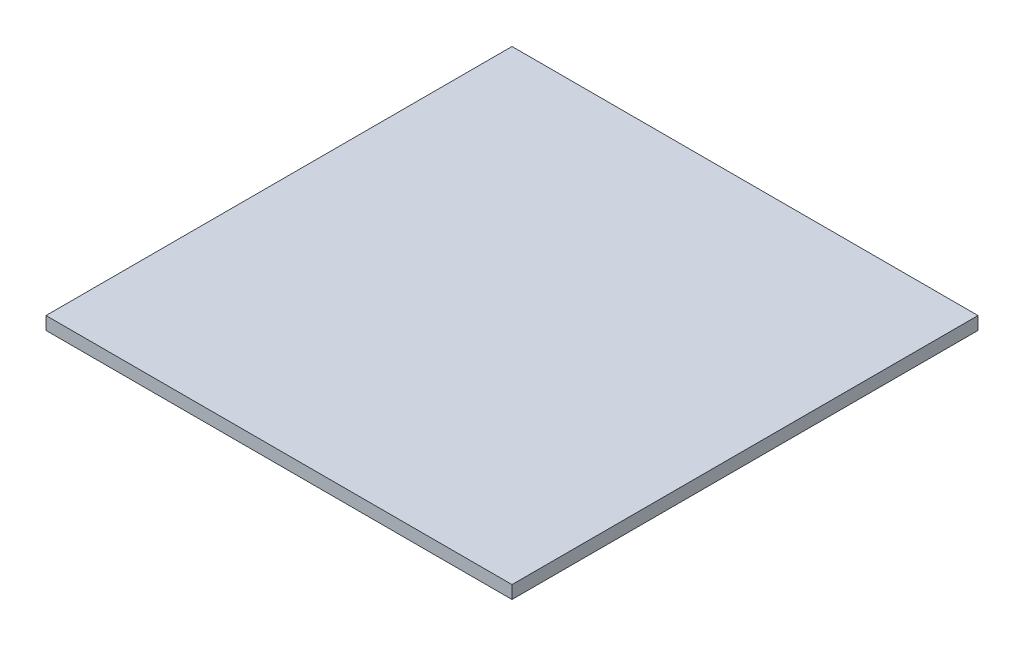
SolidWorks part; units mm, degrees
ref_plane "Front Plane" through (0, 0, 0) normal (0, 0, 1) x (1, 0, 0)
ref_plane "Top Plane" through (0, 0, 0) normal (0, 1, 0) x (1, 0, 0)
ref_plane "Right Plane" through (0, 0, 0) normal (1, 0, 0) x (0, 0, -1)
sketch "Sketch2" plane through (0, 0, 0) normal (0, 1, 0) x (1, 0, 0)
  line L1 (-90, -90) -> (90, -90)
  line L2 (-90, -90) -> (-90, 90)
  line L3 (-90, 90) -> (90, 90)
  line L4 (90, -90) -> (90, 90)
  line L5 (-90, -90) -> (90, 90) construction
  line L6 (-90, 90) -> (90, -90) construction
  point P0 (0, 0)
  dimension "D1" = 180
extrude "Boss-Extrude1" add sketch "Sketch2" along normal blind 5
